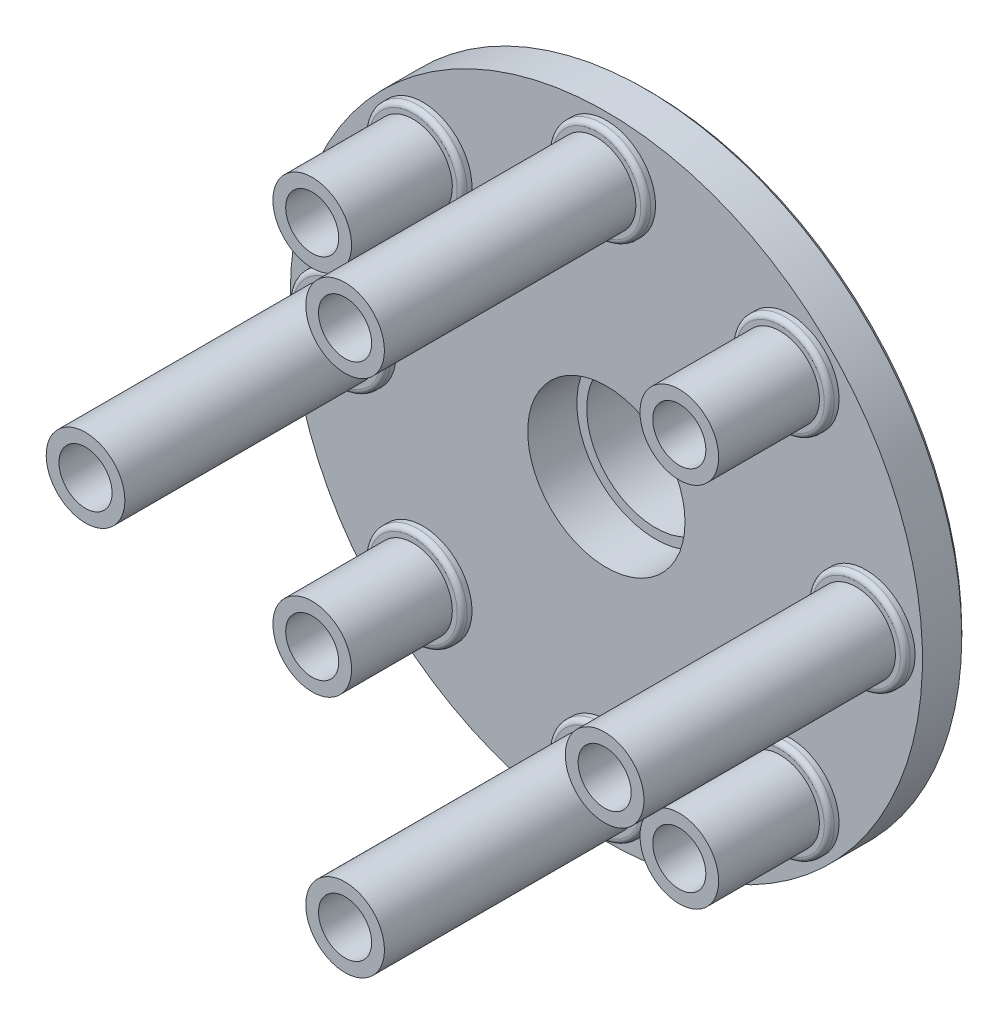
SolidWorks part; units mm, degrees
material "PLA"
ref_plane "Front Plane" through (0, 0, 0) normal (0, 0, 1) x (1, 0, 0)
ref_plane "Top Plane" through (0, 0, 0) normal (0, 1, 0) x (1, 0, 0)
ref_plane "Right Plane" through (0, 0, 0) normal (1, 0, 0) x (0, 0, -1)
ref_axis "Axis1" through (0, 0, 36.3185) along (0, 0, -1)
sketch "Sketch1" plane through (0, 0, 0) normal (0, 0, 1) x (1, 0, 0)
  circle A0 centre (0, 0) radius 32.15
  circle A1 centre (0, 0) radius 26.4 construction
  circle A2 centre (0, 26.4) radius 2.7
  circle A3 centre (26.4, 0) radius 2.7
  circle A78 centre (0, -26.4) radius 2.7
  circle A79 centre (0, 26.4) radius 4.25 construction
  circle A80 centre (0, 0) radius 30.65 construction
  circle A94 centre (-26.4, 0) radius 2.7
  point P15 (0, 0)
  dimension "D2" = 52.8
  dimension "D3" = 5.4
  dimension "D5" = 8.5
  dimension "D4" = 4
extrude "Boss-Extrude1" add sketch "Sketch1" along normal blind 4
sketch "Sketch2" plane through (0, 0, 4) normal (0, 0, 1) x (1, 0, 0)
  circle A0 centre (0, 26.4) radius 4
  circle A2 centre (0, 26.4) radius 2.7 construction
  circle A5 centre (0, 26.4) radius 2.7
  point P15 (0, 0)
  dimension "D1" = 8
extrude "Boss-Extrude2" add sketch "Sketch2" along normal blind 27.0755
sketch "Sketch3" plane through (0, 0, 4) normal (0, 0, 1) x (1, 0, 0)
  arc A2 (5, 26.4) -> (5, 26.4) centre (0, 26.4) ccw
  circle A3 centre (0, 26.4) radius 5
  circle M5 centre (0, 26.4) radius 4
extrude "Boss-Extrude3" add sketch "Sketch3" along normal blind 1.5 contours A3 M5 region at (-4.8586, 26.4, 4)
sketch "Sketch4" plane through (0, 0, 4) normal (0, 0, 1) x (1, 0, 0)
  line L0 (0, 0) -> (-22.7335, 22.7335) construction
  line L1 (0, 0) -> (0, 26.4) construction
  circle A0 centre (0, 0) radius 32.15 construction
  circle A1 centre (0, 0) radius 32.15
  circle A2 centre (0, 26.4) radius 12 construction
  circle A6 centre (0, 0) radius 26.4 construction
  arc A8 (-13.1794, 29.3245) -> (-9.5682, 16.8763) centre (0, 26.4) ccw
  circle A9 centre (0, 0) radius 19.4
  circle A11 centre (0, 0) radius 14.4 construction
  arc A13 (-29.3245, 13.1794) -> (-16.8763, 9.5682) centre (-26.4, 0) cw
  circle A16 centre (0, 26.4) radius 13.5 construction
  point P15 (0, 0)
  point P25 (0, 0)
  dimension "D1" = 24
  dimension "D5" = 28.8
  dimension "D4" = 5
  dimension "D2" = 45
  dimension "D3" = 1.5
extrude "Boss-Extrude4" [suppressed] add sketch "Sketch4" along normal blind 27.0755 contours A1 A13 A9 A8
sketch "Sketch12" [suppressed] plane through (0, 0, 37.8382) normal (0, 0, 1) x (1, 0, 0)
  arc A0 (-11.2345, 15.816) -> (-15.816, 11.2345) centre (0, 0) ccw construction
  arc A1 (-11.2345, 15.816) -> (-15.816, 11.2345) centre (0, 0) ccw
  dimension "D1" = 6.4791
fillet "Fillet2" radius 0.5 1 edges at (5, 26.4, 5.5)
fillet "Fillet5" [suppressed] radius 1.6198
pattern_circular "CirPattern1" count 8 over 360 about axis through (0, 0, 4) along (0, 0, -1) of "Fillet2", "Boss-Extrude3", "Boss-Extrude2" reverse direction yes
ref_plane "Plane1" through (0, 0, 31.0755) normal (0, 0, 1) x (1, 0, 0)
chamfer "Chamfer1" distance 0.5 angle 45 1 edges at (32.15, 0, 0)
sketch "Sketch9" plane through (0, 0, 4) normal (0, 0, 1) x (1, 0, 0)
  circle A0 centre (0, 0) radius 8
  dimension "D1" = 16
extrude "Cut-Extrude4" cut sketch "Sketch9" against normal through all
sketch "Sketch10" plane through (0, 0, 0) normal (0, 0, -1) x (-1, 0, 0)
  circle A0 centre (0, 0) radius 8 construction
  circle A1 centre (0, 0) radius 8
  circle A2 centre (0, 0) radius 6.5
extrude "Boss-Extrude7" add sketch "Sketch10" against normal blind 6.5
sketch "Sketch13" plane through (0, 0, 0) normal (0, 1, 0) x (1, 0, 0)
  line L0 (0, 0) -> (0, -31.0755) construction
  line L1 (-4, -31.0755) -> (4, -31.0755) construction
  line L2 (15.9676, -4) -> (21.3676, -4) construction
  line L3 (-32.5, 0.5) -> (-39.8, -4) construction
  line L4 (-36.9415, -4) -> (-30.4526, 0)
  line L7 (31.65, 0) -> (-31.65, 0) construction
  line L8 (0, -4) -> (-39.8, -4) construction
  line L9 (-30.4526, 0) -> (-36.9415, 0)
  line L10 (-36.9415, 0) -> (-36.9415, -4)
  dimension "D1" = 32.5
  dimension "D2" = 39.8
  dimension "D3" = 4.5
  dimension "D4" = 1.5
sketch "Sketch14" plane through (0, 0, 4) normal (0, 0, 1) x (1, 0, 0)
  circle A0 centre (0, 0) radius 16.1
  circle A1 centre (0, 0) radius 6.5 construction
  dimension "D1" = 32.2
extrude "Cut-Extrude5" cut sketch "Sketch14" against normal through all both and the other way through all
sketch "Sketch15" plane through (0, 0, 4) normal (0, 0, 1) x (1, 0, 0)
  circle A0 centre (0, 0) radius 16.1
  circle A1 centre (0, 0) radius 15.1
  circle A2 centre (0, 0) radius 16.1 construction
  dimension "D1" = 1
extrude "Boss-Extrude8" add sketch "Sketch15" against normal blind 1.5
sketch "Sketch16" plane through (0, 0, 0) normal (0, 0, -1) x (-1, 0, 0)
  circle A0 centre (0, 0) radius 18.1
  circle A1 centre (0, 0) radius 16.1 construction
  circle M1 centre (0, 0) radius 16.1
extrude "Boss-Extrude9" add sketch "Sketch16" along normal blind 4.5 contours A0 M1 region at (17.5881, 0, 0)
chamfer "Chamfer3" distance 2 distance2 4.5 1 edges at (18.1, 0, 0) first distance on face at (18.1, 0, 0)
sketch "Sketch5" [suppressed] plane through (0, 0, 32.8234) normal (0, 0, 1) x (1, 0, 0)
  line L0 (0, 0) -> (-22.4506, 22.4506) construction
  line L1 (0, 0) -> (0, 26) construction
  circle A3 centre (-19.6222, 19.6222) radius 1.7
  circle A4 centre (0, 0) radius 31.75 construction
  arc A5 (-13.189, 28.881) -> (-28.881, 13.189) centre (0, 0) ccw construction
  dimension "D2" = 3.4
  dimension "D1" = 4
  dimension "D3" = 45
extrude "Cut-Extrude1" [suppressed] cut sketch "Sketch5" against normal through all
sketch "Sketch7" plane through (0, 0, 0) normal (0, 0, -1) x (-1, 0, 0)
  circle A0 centre (0, 26.4) radius 4.45
  circle A1 centre (0, 0) radius 26.4 construction
  point P15 (0, 0)
  dimension "D1" = 8.9
extrude "Cut-Extrude3" cut sketch "Sketch7" against normal blind 5 and the other way through all
sketch "Sketch6" [suppressed] plane through (0, 0, 0) normal (0, 0, -1) x (-1, 0, 0)
  circle A0 centre (19.6222, 19.6222) radius 2.95
  dimension "D1" = 5.9
extrude "Cut-Extrude2" [suppressed] cut sketch "Sketch6" against normal blind 3 and the other way through all
pattern_circular "CirPattern2" count 8 over 360 about axis through (0, 0, 4) along (0, 0, -1) of "Cut-Extrude3" reverse direction yes
chamfer "Chamfer4" distance 0.5 angle 45 1 edges at (-16.1, 0, -4.5)
sketch "Sketch17" plane through (0, 0, 31.0755) normal (0, 0, 1) x (1, 0, 0)
  circle A0 centre (-18.6676, 18.6676) radius 6.5962
extrude "Cut-Extrude6" cut sketch "Sketch17" against normal blind 15.3255
chamfer "Chamfer5" [suppressed] distance 1 angle 45
pattern_circular "CirPattern3" count 4 over 360 about axis through (0, 0, 4) along (0, 0, 1) of "Cut-Extrude6"
sketch "Sketch19" plane through (0, 0, 2.5) normal (0, 0, -1) x (-1, 0, 0)
  circle A0 centre (0, 0) radius 15.1
  dimension "D1" = 30.2
extrude "Boss-Extrude11" add sketch "Sketch19" against normal blind 2
sketch "Sketch18" plane through (0, 0, 2.5) normal (0, 0, -1) x (-1, 0, 0)
  circle A0 centre (0, 0) radius 8
  circle A1 centre (0, 0) radius 10
  dimension "D1" = 20
  dimension "D2" = 16
extrude "Boss-Extrude10" add sketch "Sketch18" along normal blind 16 contours A0 | A1 A0 | A0 | A1 region at (0, 0, 2.5) region at (9.7172, 0, 2.5)
sketch "Sketch20" plane through (0, 0, 4.5) normal (0, 0, 1) x (1, 0, 0)
  circle A3 centre (0, 0) radius 8
  circle A4 centre (0, 0) radius 8
  dimension "D2" = 0
extrude "Cut-Extrude7" cut sketch "Sketch20" against normal blind 6.5
sketch "Sketch21" plane through (0, 0, -13.5) normal (0, 0, -1) x (-1, 0, 0)
  circle A0 centre (0, 0) radius 6 construction
  circle A1 centre (0, 6) radius 2
  dimension "D1" = 12
  dimension "D2" = 4
sketch "Sketch22" plane through (0, 0, -13.5) normal (0, 0, -1) x (-1, 0, 0)
  line L0 (-3.5, 3.9793) -> (-3.5, 12.0622)
  line L1 (3.5, 8.0207) -> (0, 10.0415)
  line L2 (0, 10.0415) -> (-3.5, 8.0207)
  line L3 (-3.5, 8.0207) -> (-3.5, 3.9793)
  line L4 (-3.5, 3.9793) -> (0, 1.9585)
  line L5 (0, 1.9585) -> (3.5, 3.9793)
  line L6 (3.5, 3.9793) -> (3.5, 8.0207)
  line L7 (-3.5, 12.0622) -> (3.5, 12.0622)
  line L8 (3.5, 12.0622) -> (3.5, 7.3632)
  circle A0 centre (0, 6) radius 3.5 construction
  dimension "D1" = 7
sketch "Sketch23" plane through (0, 0, 4.5) normal (0, 0, 1) x (1, 0, 0)
  circle A0 centre (0, 0) radius 7
  circle A3 centre (0, 0) radius 8
  circle A4 centre (0, 0) radius 8
  circle M4 centre (0, 0) radius 8
  dimension "D1" = 1
  dimension "D2" = 0
extrude "Boss-Extrude12" add sketch "Sketch23" against normal up to surface (6.5 mm away) from offset 5 contours A0 M4 region at (-7.7737, 0, 4.5) up to face at (8, 0, -2) offset against normal yes
chamfer "Chamfer6" distance 0.5 angle 45 1 edges at (-10, 0, -13.5)
sketch "Sketch24" plane through (0, 0, -2) normal (0, 0, 1) x (1, 0, 0)
  circle A1 centre (0, 0) radius 7
  circle A2 centre (0, 0) radius 7
  dimension "D1" = 0
extrude "Cut-Extrude8" cut sketch "Sketch24" against normal through all both and the other way through all
sketch "Sketch25" plane through (0, 0, 4) normal (0, 0, 1) x (1, 0, 0)
  circle A1 centre (0, 0) radius 32.15
  circle A2 centre (0, 0) radius 32.15
  circle M2 centre (18.6676, 18.6676) radius 5
  circle M3 centre (26.4, 0) radius 5
  circle M4 centre (18.6676, -18.6676) radius 5
  circle M5 centre (0, -26.4) radius 5
  circle M6 centre (-18.6676, -18.6676) radius 5
  circle M7 centre (-26.4, 0) radius 5
  circle M8 centre (-18.6676, 18.6676) radius 5
  circle M9 centre (0, 0) radius 32.15
  circle M10 centre (0, 26.4) radius 5
  circle M11 centre (0, 0) radius 15.1
  dimension "D1" = 0
extrude "Boss-Extrude13" add sketch "Sketch25" along normal up to surface (0.5 mm away) contours M9 M3 M5 M7 M11 M10 M8 M6 M4 M2 region at (-32.0591, 0, 4) up to face at (8, 0, 4.5)
equation "\"Nr_s\" = 116"
equation "\"module\" = 0.6"
equation "\"pressure_angle\" = 20.0"
equation "\"h_a\" = 0.6"
equation "\"h_f\" = 0.75"
equation "\"clr_tip_root\" = 0.15000000000000002"
equation "\"dp_r_s\" = 69.6"
equation "\"db_r\"= \"dp_r_s\" * cos ( \"pressure_angle\" )'base CD"
equation "\"bearing_ID\" = 65"
equation "\"bearing_OD\" = 85"
equation "\"bearing_height\" = 10"
equation "\"clearance_planet\" = 1.5"
equation "\"case_dist\" = 6.5"
equation "\"Motor_case_OD_max\" = 115.5"
equation "\"case_mounting_PCD\" = 108.0"
equation "\"bearing mount thickness\" = 8"
equation "\"case_mounting_hole_dia\" = 3"
equation "\"output_mounting_PCD\" = 93"
equation "\"output_mounting_hole_dia\" = 4"
equation "\"clearance_case_mount_holes_shell_thickness\" = 1"
equation "\"motor_case_OD_base\" = 106.0"
equation "\"sec_carrier_thickness\" = 5"
equation "\"sun_coupler_hub_thickness\" = 4"
equation "\"clearance_sun_coupler_sec_carrier\" = 1.5"
equation "\"clearance_motor_and_case\" = 14.5"
equation "\"motor_OD\" = 72"
equation "\"Motor_case_thickness\" = 2.5"
equation "\"Motor_case_ID\" = 101.0"
equation "\"case_mounting_hole_shift\" = 1.0"
equation "\"output_mounting_nut_wrench_size\" = 7"
equation "\"output_mounting_nut_thickness\" = 3.2"
equation "\"case_mounting_hole_allen_socket_dia\" = 5.5"
equation "\"output_mounting_nut_depth\" = 3"
equation "\"case_mounting_bolt_depth\" = 4.5"
equation "\"Ns\" = 48"
equation "\"Np_b\" = 40"
equation "\"ring_radial_thickness\" = 5"
equation "\"ring_OD\"= \"Nr_s\" * \"module\" + \"ring_radial_thickness\" * 2"
equation "\"ring_to_chamfer_clearance\" = 1.5"
equation "\"Motor_case_OD_base_to_chamfer\" = 5"
equation "\"pattern_offset_from_motor_case_OD_base\" = 3"
equation "\"pattern_bulge_dia\" = 3"
equation "\"pattern_num_bulge\" = 18"
equation "\"pattern_depth\" = 2"
equation "\"motor_height\" = 27"
equation "\"case_mounting_wrench_size\" = 5.5"
equation "\"case_mounting_nut_clearance\" = 2"
equation "\"base_plate_thickness\" = 4"
equation "\"case_mounting_nut_thickness\" = 2.4"
equation "\"case_mounting_surface_height\" = 4"
equation "\"motor_mount_hole_PCD\" = 32"
equation "\"motor_mount_hole_dia\" = 4"
equation "\"motor_mount_hole_num\" = 4"
equation "\"central_hole_offset_from_motor_mount_PCD\" = 5"
equation "\"wire_slot_dist_from_center\" = 26"
equation "\"wire_slot_length\" = 10"
equation "\"wire_slot_radius\" = 2.5"
equation "\"driver_upper_holes_dist_from_center\" = 29"
equation "\"driver_lower_holes_dist_from_center\" = 13"
equation "\"driver_side_holes_dist_from_center\" = 22.5"
equation "\"driver_mount_holes_dia\" = 3"
equation "\"driver_mount_inserts_OD\" = 4.8"
equation "\"driver_mount_thickness\" = 1.5"
equation "\"driver_mount_height\" = 6"
equation "\"air_flow_hole_offset\" = 3"
equation "\"num_planet\" = 4"
equation "\"planet_pin_bolt_dia\" = 5"
equation "\"planet_pin_socket_head_dia\" = 8.5"
equation "\"carrier_PCD\" = 52.8"
equation "\"D2@Sketch1\"=\"carrier_PCD\""
equation "\"D3@Sketch1\"=\"planet_pin_bolt_dia\" + \"tight_clearance_3DP\""
equation "\"D4@Sketch1\"=\"num_planet\""
equation "\"D1@Boss-Extrude2\" = \"fw_p_s\" + \"clearance_planet\" * 2 + \"fw_p_b\""
equation "\"D1@Boss-Extrude3\"=\"clearance_planet\""
equation "\"D1@Sketch4\"=\"Np_b\"*\"module\""
equation "\"D3@Sketch4\"=\"clearance_planet\""
equation "\"D1@Boss-Extrude4\" = \"fw_p_s\" + \"clearance_planet\" * 2 + \"fw_p_b\""
equation "\"D1@Fillet2\"=\"clearance_planet\"/3"
equation "\"D1@CirPattern1\"=2*\"num_planet\""
equation "\"D1@CirPattern2\"=2*\"num_planet\""
equation "\"D1@Boss-Extrude7\"=\"bearing_height\"+ \"carrier_bearing_step_width\" - \"sun_shaft_bearing_width\""
equation "\"planet_shaft_dia\" = 8"
equation "\"D1@Sketch2\"= \"planet_shaft_dia\""
equation "\"planet_shaft_step_offset\" = 1"
equation "\"D1@Sketch3\"=\"planet_shaft_step_offset\""
equation "\"carrier_trapezoidal_support_sun_offset\" = 5"
equation "\"D4@Sketch4\"=\"carrier_trapezoidal_support_sun_offset\""
equation "\"carrier_trapezoidal_support_hole_PCD_offset_bearing_ID\" = 4"
equation "\"carrier_trapezoidal_support_hole_dia\" = 3"
equation "\"D2@Sketch5\"=\"carrier_trapezoidal_support_hole_dia\" + \"tight_clearance_3DP\""
equation "\"D1@Cut-Extrude2\"=\"carrier_trapezoidal_support_hole_dia\""
equation "\"carrier_trapezoidal_support_hole_socket_head_dia\" = 5.5"
equation "\"D1@Sketch6\"=\"carrier_trapezoidal_support_hole_socket_head_dia\" +  \"tight_clearance_3DP\""
equation "\"D1@Cut-Extrude3\"=\"planet_pin_bolt_dia\""
equation "\"D1@Sketch7\"=\"planet_pin_socket_head_dia\" + \"tight_clearance_3DP\""
equation "\"carrier_bearing_step_width\" = 1.5"
equation "\"standard_clearance_1_5mm\" = 1.5"
equation "\"standard_fillet_1_5mm\" = 1.5"
equation "\"sun_shaft_bearing_OD\" = 16"
equation "\"D1@Sketch9\"=\"sun_shaft_bearing_OD\""
equation "\"D1@Sketch10\"=\"standard_clearance_1_5mm\""
equation "\"sun_shaft_bearing_width\" = 5"
equation "\"standard_bearing_insertion_chamfer\" = 0.5"
equation "\"D1@Chamfer1\"=\"standard_bearing_insertion_chamfer\""
equation "\"D5@Sketch4\"=\"Ns\"*\"module\""
equation "\"D1@Sketch5\"=\"carrier_trapezoidal_support_hole_PCD_offset_bearing_ID\""
equation "\"D1@Plane1\" = \"fw_p_s\" + \"clearance_planet\" * 2 + \"fw_p_b\""
equation "\"D2@Sketch4\"=180/\"num_planet\""
equation "\"D3@Sketch5\"=180/\"num_planet\""
equation "\"carrier_trapezoidal_support_hole_wrench_size\" = 5.5"
equation "\"planet_pin_bolt_wrench_size\" = 8"
equation "\"pressure angle\" = 20.0"
equation "\"h_b\" = 0.75"
equation "\"dp_s\" = 28.799999999999997"
equation "\"db_s\" = 27.06314747863416"
equation "\"fw_s_calc\" = 2.359230083666351"
equation "\"alpha_s\" = 0.8539582918412343"
equation "\"beta_s\" = 2.0420834163175314"
equation "\"dp_p_b\" = 24.0"
equation "\"db_p_b\" = 22.552622898861802"
equation "\"fw_p_s\" = 11.6295029769434"
equation "\"alpha_p_b\" = 0.8539582918412414"
equation "\"beta_p_b\" = 2.792083416317517"
equation "\"planet_bearing_OD\" = 12"
equation "\"planet_bearing_width\" = 3.5"
equation "\"planet_bore\" = 10"
equation "\"motor_output_hole_PCD\" = 22"
equation "\"motor_output_hole_dia\" = 3"
equation "\"motor_output_hole_num\" = 4"
equation "\"sun_shaft_bearing_ID\" = 8"
equation "\"sun_hub_dia\" = 28.0"
equation "\"sun_central_bolt_dia\" = 5"
equation "\"sun_central_bolt_socket_head_dia\" = 8.5"
equation "\"fw_s_used\" = 31.575468444261382"
equation "\"motor_output_hole_CSK_OD\" = 6"
equation "\"motor_output_hole_CSK_head_height\" = 1.5"
equation "\"bearing_retainer_thickness\" = 2"
equation "\"Np_s\" = 28"
equation "\"fw_p_b\" = 12.445965467317981"
equation "\"dp_p_s\" = 16.8"
equation "\"db_p_s\" = 15.786836029203263"
equation "\"alpha_p_s\" = 0.8539582918412343"
equation "\"beta_p_s\" = 4.72065484488896"
equation "\"Nr_b\" = 128"
equation "\"dp_r_b\" = 76.8"
equation "\"db_r_b\" = 72.16839327635776"
equation "\"fw_r_b\" = 12.445965467317981"
equation "\"alpha_r_b\" = 0.8539582918412556"
equation "\"beta_r_b\" = 3.114166583682511"
equation "\"ring_OD_b\" = 86.8"
equation "\"Fillet11\"= IIF ( \"ring_OD_b\" < ( \"bearing_OD\" + 2 * \"bearing mount thickness\" ) , \"suppressed\" , \"unsuppressed\" )"
equation "\"clr_tip_root_s\" = 0.15000000000000002"
equation "\"db_r_s\" = 65.40260640669922"
equation "\"fw_r_s\" = 10.1295029769434"
equation "\"alpha_r_s\" = 0.8539582918412343"
equation "\"beta_r_s\" = 3.2596407216135033"
equation "\"D1@Sketch13\"=\"bearing_ID\"/2"
equation "\"D2@Sketch13\"=(\"Nr_s\"*\"module\"+\"ring_radial_thickness\"*2)*0.5"
equation "\"D3@Sketch13\"=\"standard_clearance_1_5mm\"*3"
equation "\"D4@Sketch13\"=\"standard_clearance_1_5mm\""
equation "\"D5@Sketch1\"=\"planet_pin_socket_head_dia\""
equation "\"D1@Sketch1\"=\"standard_clearance_1_5mm\""
equation "\"small_ring_case_thickness\" = 4"
equation "\"carrier_thickness\" = 4"
equation "\"small_ring_output_wall_thickness\" = 5"
equation "\"small_ring_output_wall_to_bearing_shaft_attachement_hole_dia\" = 4"
equation "\"small_ring_output_wall_to_bearing_shaft_attachement_hole_depth\" = 6.5"
equation "\"small_ring_output_wall_to_bearing_shaft_attachement_nut_wrench\" = 7"
equation "\"small_ring_output_wall_to_bearing_shaft_attachement_nut_thickness\" = 3.2"
equation "\"small_ring_output_wall_to_bearing_shaft_attachement_hole_pcd\" = 12"
equation "\"small_ring_output_wall_to_bearing_shaft_attachement_hole_num\" = 3"
equation "\"small_ring_output_wall_to_bearing_shaft_attachement_hole_CSK_OD\" = 8"
equation "\"small_ring_output_wall_to_bearing_shaft_attachement_hole_CSK_head_height\" = 2.0"
equation "\"carrier_small_ring_inner_bearing_ID\" = 20"
equation "\"carrier_small_ring_inner_bearing_OD\" = 32"
equation "\"carrier_small_ring_inner_bearing_height\" = 7"
equation "\"carrier_small_ring_inner_bearing_flap\" = 2"
equation "\"gear_casing_big_ring_to_bearing_dist\" = 20.6295029769434"
equation "\"gear_casing_thickness\" = 4"
equation "\"D1@Boss-Extrude1\"=\"carrier_thickness\""
equation "\"D1@Boss-Extrude9\"= \"carrier_small_ring_inner_bearing_height\" - \"carrier_thickness\" + \"standard_clearance_1_5mm\""
equation "\"D3@Chamfer3\"=\"carrier_small_ring_inner_bearing_height\"-\"carrier_thickness\" + \"standard_clearance_1_5mm\""
equation "\"D1@Chamfer3\"=\"standard_clearance_1_5mm\"*4/3"
equation "\"D1@Sketch14\"=\"carrier_small_ring_inner_bearing_OD\" + \"tight_clearance_3DP\"/2"
equation "\"D1@Sketch16\"=\"standard_clearance_1_5mm\"*4/3"
equation "\"tight_clearance_3DP\" = 0.4"
equation "\"loose_clearance_3DP\" = 0.8"
equation "\"D1@Chamfer4\"= \"standard_bearing_insertion_chamfer\""
equation "\"D1@Cut-Extrude6\"=\"fw_p_s\" + \"clearance_planet\" * 2 + \"fw_p_b\" - \"fw_idler\"-3mm"
equation "\"D1@CirPattern3\"=\"num_planet\""
equation "\"Ns_fs\" = 60"
equation "\"dp_fs\" = 36.0"
equation "\"db_fs\" = 33.828934348292705"
equation "\"alpha_fs\" = 0.8539582918412343"
equation "\"beta_fs\" = 1.2920834163175314"
equation "\"fw_fs\" = 11.6295029769434"
equation "\"num_idler\" = 4"
equation "\"idler_angle_offset\" = 45.0"
equation "\"fw_idler\" = 8.75"
equation "\"D1@Sketch18\"=\"carrier_small_ring_inner_bearing_ID\""
equation "\"D2@Sketch18\"=\"sun_shaft_bearing_OD\""
equation "\"D1@Sketch19\"=\"carrier_small_ring_inner_bearing_OD\" + \"tight_clearance_3DP\"/2 -2mm"
equation "\"D1@Boss-Extrude11\"=\"carrier_small_ring_inner_bearing_flap\""
equation "\"D1@Cut-Extrude7\"=\"sun_shaft_bearing_width\" + \"standard_clearance_1_5mm\""
equation "\"D1@Sketch21\"=\"small_ring_output_wall_to_bearing_shaft_attachement_hole_pcd\""
equation "\"D2@Sketch21\"=\"small_ring_output_wall_to_bearing_shaft_attachement_hole_dia\""
equation "\"D1@Cut-Extrude8\"=\"small_ring_output_wall_to_bearing_shaft_attachement_hole_depth\""
equation "\"D1@Sketch22\"=\"small_ring_output_wall_to_bearing_shaft_attachement_nut_wrench\""
equation "\"D19@Boss-Extrude12\"=\"sun_shaft_bearing_width\""
equation "\"D1@Chamfer6\"=\"standard_bearing_insertion_chamfer\""
equation "\"D1@Boss-Extrude10\"=\"bearing_height\" + \"carrier_thickness\" + \"carrier_small_ring_inner_bearing_flap\""
equation "\"Fillet10\"= IIF ( \"ring_OD_b\" > ( \"bearing_OD\" + 2 * \"bearing mount thickness\" ) , \"suppressed\" , \"unsuppressed\" )"
equation "\"D1@CirPattern5\"=\"small_ring_output_wall_to_bearing_shaft_attachement_hole_num\""
equation "\"D19@Cut-Extrude9\"=\"standard_clearance_1_5mm\"*2"
equation "\"D1@CirPattern4\"=\"small_ring_output_wall_to_bearing_shaft_attachement_hole_num\""
